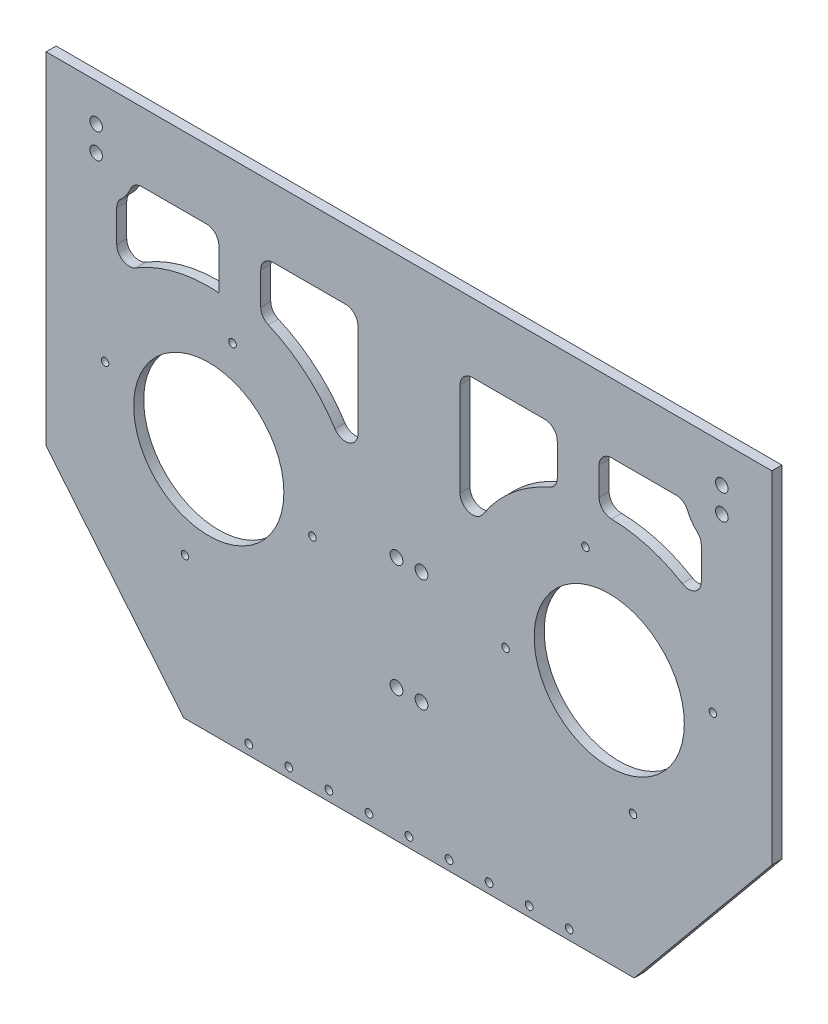
SolidWorks part; units mm, degrees
ref_plane "Front Plane" through (0, 0, 0) normal (0, 0, 1) x (1, 0, 0)
ref_plane "Top Plane" through (0, 0, 0) normal (0, 1, 0) x (1, 0, 0)
ref_plane "Right Plane" through (0, 0, 0) normal (1, 0, 0) x (0, 0, -1)
sketch "Sketch1" plane through (0, 0, 0) normal (0, 0, 1) x (1, 0, 0)
  line L0 (-125, 100) -> (125, 100) construction
  line L1 (-125, 0) -> (125, 0) construction
  line L2 (-145, -16.3871) -> (-90, -83)
  line L4 (90, -83) -> (145, -16.3871)
  line L5 (-125, 105) -> (-125, 95) construction
  line L6 (0, -55) -> (0, 100) construction
  line L7 (-145, 120) -> (145, 120)
  line L8 (145, 120) -> (145, -16.3871)
  line L11 (-145, -16.3871) -> (-145, 120)
  line L12 (125, 105) -> (125, 95) construction
  line L16 (-90, -83) -> (90, -83)
  circle A0 centre (-125, 100) radius 12.5 construction
  circle A10 centre (-125, 0) radius 12.5 construction
  circle A11 centre (125, 0) radius 12.5 construction
  circle A12 centre (-125, 0) radius 17.5 construction
  circle A13 centre (-125, 100) radius 17.5 construction
  circle A25 centre (-125, 95) radius 2.5
  circle A26 centre (-125, 105) radius 2.5
  circle A27 centre (125, 95) radius 2.5
  circle A28 centre (125, 105) radius 2.5
  circle A32 centre (5, 15) radius 2.55
  circle A33 centre (5, -30) radius 2.55
  circle A34 centre (-5, -30) radius 2.55
  circle A35 centre (-5, 15) radius 2.55
  point P12 (0, 100)
  point P15 (0, -34.3933)
  point P45 (0, 120)
  dimension "D1" = 25
  dimension "D2" = 5
  dimension "D17" = 5.1
  dimension "D4" = 100
  dimension "D6" = 5
  dimension "D11" = 20
  dimension "D12" = 20
  dimension "D7" = 10
  dimension "D8" = 250
  dimension "D15" = 5
  dimension "D16" = 45
extrude "Boss-Extrude1" add sketch "Sketch1" along normal blind 4 contours L7 L16 A27 A26 A25 A28 region at (0, 23.7, 0)
sketch "Sketch2" plane through (0, 0, 4) normal (0, 0, 1) x (1, 0, 0)
  line L0 (121.4264, 24.4924) -> (38.5736, 5.5076) construction
  line L1 (89.4924, -26.4264) -> (70.5076, 56.4264) construction
  line L2 (0, 0) -> (0, 120) construction
  line L5 (-80, 15) -> (80, 15) construction
  line L6 (-5, 15) -> (5, 15) construction
  line L8 (-149, 120) -> (-149, -18.4662) construction
  line L9 (145, 120) -> (-145, 120) construction
  circle A0 centre (80, 15) radius 42.5 construction
  circle A1 centre (38.5736, 5.5076) radius 1.5
  circle A2 centre (70.5076, 56.4264) radius 1.5
  circle A3 centre (121.4264, 24.4924) radius 1.5
  circle A4 centre (89.4924, -26.4264) radius 1.5
  circle A5 centre (80, 15) radius 30
  circle A6 centre (-38.5736, 5.5076) radius 1.5
  circle A7 centre (-70.5076, 56.4264) radius 1.5
  circle A8 centre (-89.4924, -26.4264) radius 1.5
  circle A9 centre (-121.4264, 24.4924) radius 1.5
  circle A10 centre (-80, 15) radius 42.5 construction
  circle A11 centre (-80, 15) radius 30
  circle A12 centre (-80, 15) radius 47.5 construction
  point P6 (80, 15)
  point P27 (-80, 15)
  point P30 (0, 15)
  dimension "D1" = 85
  dimension "D2" = 3
  dimension "D3" = 60
  dimension "D4" = 95
  dimension "D5" = 69
  dimension "D6" = 41.4264
  dimension "D7" = 105
  dimension "D8" = 10
extrude "Cut-Extrude1" cut sketch "Sketch2" against normal blind 10 contours A11 | A5 | A7 | A9 | A8 | A2 | A1 | A3 | A4 | A6 region at (38.5736, 5.5076, 4) region at (70.5076, 56.4264, 4) region at (121.4264, 24.4924, 4) region at (89.4924, -26.4264, 4) region at (80, 15, 4) region at (-70.5076, 56.4264, 4) region at (-89.4924, -26.4264, 4) region at (-121.4264, 24.4924, 4) region at (-80, 15, 4)
sketch "Sketch3" plane through (0, 0, 4) normal (0, 0, 1) x (1, 0, 0)
  line L1 (-90, -59.8873) -> (-90, -55) construction
  line L3 (-90, -83) -> (90, -83) construction
  circle A4 centre (-64, -79) radius 1.55
  circle A5 centre (-48, -79) radius 1.55
  circle A6 centre (-32, -79) radius 1.55
  circle A7 centre (-16, -79) radius 1.55
  circle A8 centre (0, -79) radius 1.55
  circle A9 centre (16, -79) radius 1.55
  circle A10 centre (32, -79) radius 1.55
  circle A11 centre (48, -79) radius 1.55
  circle A12 centre (64, -79) radius 1.55
  dimension "D2" = 3.1
  dimension "D1" = 4
  dimension "D3" = 26
  dimension "D5" = 9
extrude "Cut-Extrude2" cut sketch "Sketch3" against normal through all contours A4 | A5 | A6 | A12 | A11 | A10 | A7 | A8 | A9 region at (-64, -79, 4) region at (-48, -79, 4) region at (-32, -79, 4) region at (32, -79, 4) region at (48, -79, 4) region at (64, -79, 4)
sketch "Sketch6" plane through (0, 0, 0) normal (0, 0, -1) x (-1, 0, 0)
  line L0 (-20.3921, 20.3957) -> (-20.3921, 92.4562)
  line L1 (-20.3921, 92.4562) -> (-59.2398, 92.4562)
  line L2 (-59.2398, 92.4562) -> (-59.2398, 71.1358)
  line L3 (-75.9623, 92.4562) -> (-110.4197, 92.4562)
  line L4 (-75.9623, 92.4562) -> (-75.9623, 71.1358)
  line L5 (-116.7764, 82.6944) -> (-116.7764, 57.603)
  line L6 (0, -55) -> (0, 120) construction
  line L7 (90, -55) -> (-90, -55) construction
  line L8 (-145, 120) -> (145, 120) construction
  line L9 (20.3921, 20.3957) -> (20.3921, 92.4562)
  line L10 (20.3921, 92.4562) -> (59.2398, 92.4562)
  line L11 (59.2398, 92.4562) -> (59.2398, 71.1358)
  line L12 (75.9623, 92.4562) -> (75.9623, 71.1358)
  line L13 (75.9623, 92.4562) -> (110.4197, 92.4562)
  line L14 (116.7764, 82.6944) -> (116.7764, 57.603)
  arc A0 (-20.3921, 20.3957) -> (-59.2398, 71.1358) centre (-80, 15) ccw
  arc A1 (-75.9623, 71.1358) -> (-116.7764, 57.603) centre (-80, 15) ccw
  arc A2 (-110.4197, 92.4562) -> (-116.7764, 82.6944) centre (-125, 95) cw
  arc A3 (20.3921, 20.3957) -> (59.2398, 71.1358) centre (80, 15) cw
  arc A4 (75.9623, 71.1358) -> (116.7764, 57.603) centre (80, 15) cw
  arc A5 (110.4197, 92.4562) -> (116.7764, 82.6944) centre (125, 95) ccw
extrude "Cut-Extrude3" cut sketch "Sketch6" against normal through all contours L3 A2 L5 A1 L4 | A0 L0 L1 L2 | L9 A3 L11 L10 | A5 L13 L12 A4 L14 region at (36.1386, 72.1325, 0) region at (97.4759, 79.2288, 0) region at (-36.1386, 72.1325, 0) region at (-97.4759, 79.2288, 0)
fillet "Fillet1" radius 5 17 edges at (-59.2398, 92.4562, 2) (-110.4197, 92.4562, 2) (-116.7764, 82.6944, 2) (-59.2398, 71.1358, 2) (-116.7764, 57.603, 2) (-75.9623, 92.4562, 2) (-20.3921, 92.4562, 2) (-20.3921, 20.3957, 2) (20.3921, 20.3957, 2) (59.2398, 92.4562, 2) (59.2398, 71.1358, 2) (20.3921, 92.4562, 2) (75.9623, 92.4562, 2) (75.9623, 71.1358, 2) (110.4197, 92.4562, 2) (116.7764, 82.6944, 2) (116.7764, 57.603, 2)
fillet "Fillet2" radius 0.5 rebuild error yes
fillet "Fillet3" radius 10 rebuild error yes
equation "\"D1@Sketch1\" = \"cf_tube_outer_diameter\""
equation "\"mid_plate_mid_to_top\" = 100mm"
equation "\"mid_plate_mid_to_bottom\" = 30mm"
equation "\"mid_plate_horizontal_spacing\"=250mm"
equation "\"cf_tube_outer_diameter\"= 25mm"
equation "\"D4@Sketch1\"=\"mid_plate_mid_to_top\""
equation "\"cf_tube_inner_diameter\" = 21mm"
equation "\"mid_tube_length\" = 121mm"
equation "\"cf_plate_thickness\" =4mm"
equation "\"D1@Boss-Extrude1\"=\"cf_plate_thickness\""
equation "\"D8@Sketch1\"=\"mid_plate_horizontal_spacing\""
equation "\"mid_plate_bottom_width\" = 180mm"
equation "\"mid_support_plate_distance\" = 250mm"
equation "\"nut_strip_2_hole_distance\" = 7mm"
equation "\"nut_strip_hole_diameter\" = 2.5mm"
equation "\"nut_strip_hole_to_edge_distance\"= 2.5mm"
